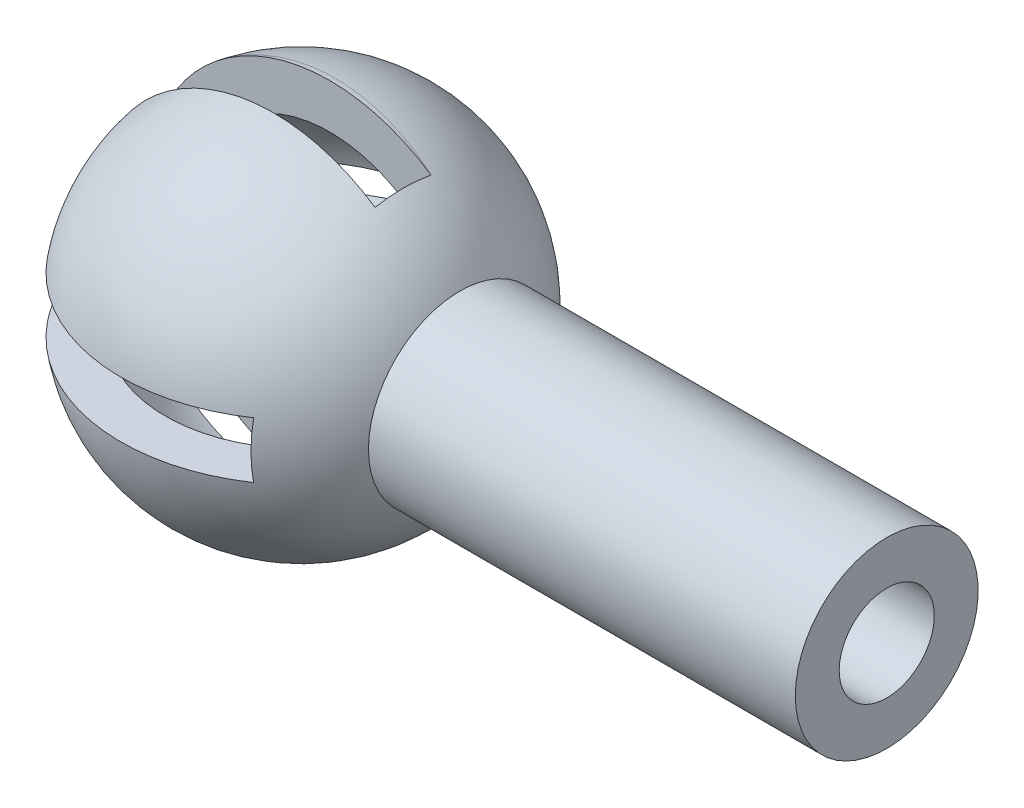
SolidWorks part; units mm, degrees
ref_plane "Front" through (0, 0, 0) normal (0, 0, 1) x (1, 0, 0)
ref_plane "Top" through (0, 0, 0) normal (0, 1, 0) x (1, 0, 0)
ref_plane "Right" through (0, 0, 0) normal (1, 0, 0) x (0, 0, -1)
sketch "Sketch1" plane through (0, 0, 0) normal (0, 0, 1) x (1, 0, 0)
  line L0 (9.5, 0) -> (48.6866, 0) construction
  line L1 (40, 6.25) -> (10.8253, 6.25)
  line L2 (40, 6.25) -> (40, 3.25)
  line L3 (40, 3.25) -> (15, 3.25)
  line L9 (15, 3.25) -> (15, 0)
  line L10 (-12.339, 2) -> (-9.2871, 2)
  line L11 (9.5, 0) -> (15, 0)
  arc A0 (10.8253, 6.25) -> (-12.339, 2) centre (0, 0) ccw
  arc A1 (9.5, 0) -> (-9.2871, 2) centre (0, 0) ccw
  point P3 (48.6866, 0)
  point P11 (15, 0)
  dimension "D1" = 6.5
  dimension "D2" = 12.5
  dimension "D6" = 3
  dimension "D3" = 3
  dimension "D4" = 25
  dimension "D5" = 15
  dimension "D7" = 2
revolve "Revolve1" add sketch "Sketch1" angle 360 about L0
sketch "Sketch2" plane through (0, 0, 0) normal (0, 0, 1) x (1, 0, 0)
  line L1 (-15.729, 1.9156) -> (6.9395, 1.9156)
  line L2 (-15.729, 1.9156) -> (-15.729, -1.9156)
  line L3 (-15.729, -1.9156) -> (6.9395, -1.9156)
  line L4 (6.9395, 1.9156) -> (6.9395, -1.9156)
  line L5 (-15.729, 1.9156) -> (6.9395, -1.9156) construction
  line L6 (-15.729, -1.9156) -> (6.9395, 1.9156) construction
  point P0 (-4.3947, 0)
extrude "Cut-Extrude1" cut sketch "Sketch2" along normal through all
pattern_circular "CirPattern1" count 4 over 360 about axis through (9.5, 0, 0) along (-1, 0, 0) of "Cut-Extrude1" reverse direction yes
